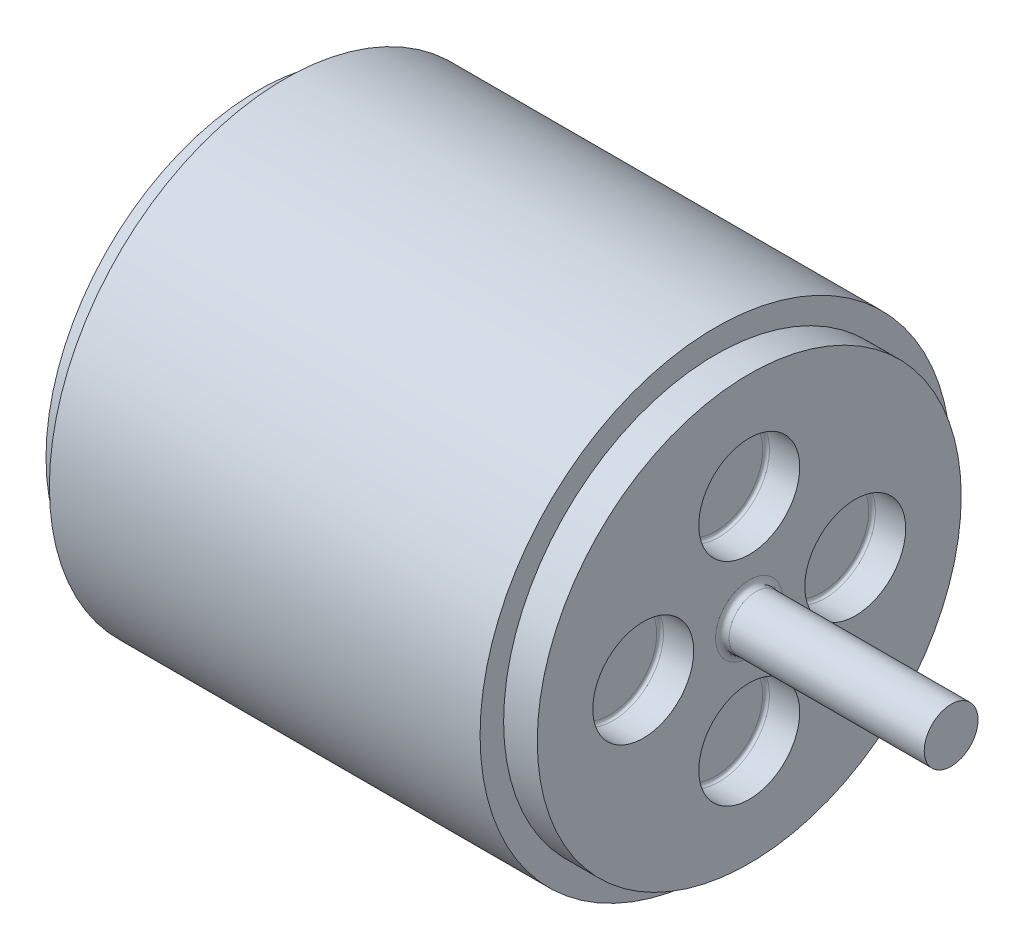
SolidWorks part; units mm, degrees
ref_plane "Front Plane" through (0, 0, 0) normal (0, 0, 1) x (1, 0, 0)
ref_plane "Top Plane" through (0, 0, 0) normal (0, 1, 0) x (1, 0, 0)
ref_plane "Right Plane" through (0, 0, 0) normal (1, 0, 0) x (0, 0, -1)
sketch "Sketch1" plane through (0, 0, 0) normal (1, 0, 0) x (0, 0, -1)
  circle A0 centre (0, 0) radius 31.5
  dimension "D1" = 63
extrude "Boss-Extrude1" add sketch "Sketch1" along normal blind 73
sketch "Sketch3" plane through (0, 0, 0) normal (-1, 0, 0) x (0, 0, 1)
  circle A1 centre (0, 0) radius 4
  dimension "D1" = 8
extrude "Boss-Extrude3" add sketch "Sketch3" against normal blind 103
sketch "Sketch4" plane through (73, 0, 0) normal (1, 0, 0) x (0, 0, -1)
  circle A0 centre (0, 15.75) radius 7.5
  circle A1 centre (15.75, 0) radius 7.5
  circle A2 centre (0, -15.75) radius 7.5
  circle A3 centre (-15.75, 0) radius 7.5
  dimension "D1" = 15
  dimension "D2" = 15
  dimension "D3" = 15
  dimension "D4" = 15
  dimension "D5" = 15.75
  dimension "D6" = 15.75
  dimension "D7" = 15.75
  dimension "D8" = 15.75
extrude "Boss-Extrude4" add sketch "Sketch4" against normal blind 5
extrude "Cut-Extrude1" cut sketch "Sketch4<2>" against normal blind 5
sketch "Sketch4<2>" plane through (73, 0, 0) normal (1, 0, 0) x (0, 0, -1) same geometry as "Sketch4"
sketch "Sketch5" plane through (103, 0, 0) normal (1, 0, 0) x (0, 0, -1)
  circle A0 centre (0, 0) radius 35
  point P3 (-1.1745, 32.1318)
  dimension "D1" = 70
extrude "Boss-Extrude5" add sketch "Sketch5" against normal blind 64 from offset 35 offset against normal yes
fillet "Fillet4" radius 1 1 edges at (73, 0, -4) curvature continuous yes
fillet "Fillet5" radius 0.5 4 edges at (68, -15.75, -7.5) (68, 0, 8.25) (68, 0, -23.25) (68, 15.75, -7.5) curvature continuous yes
